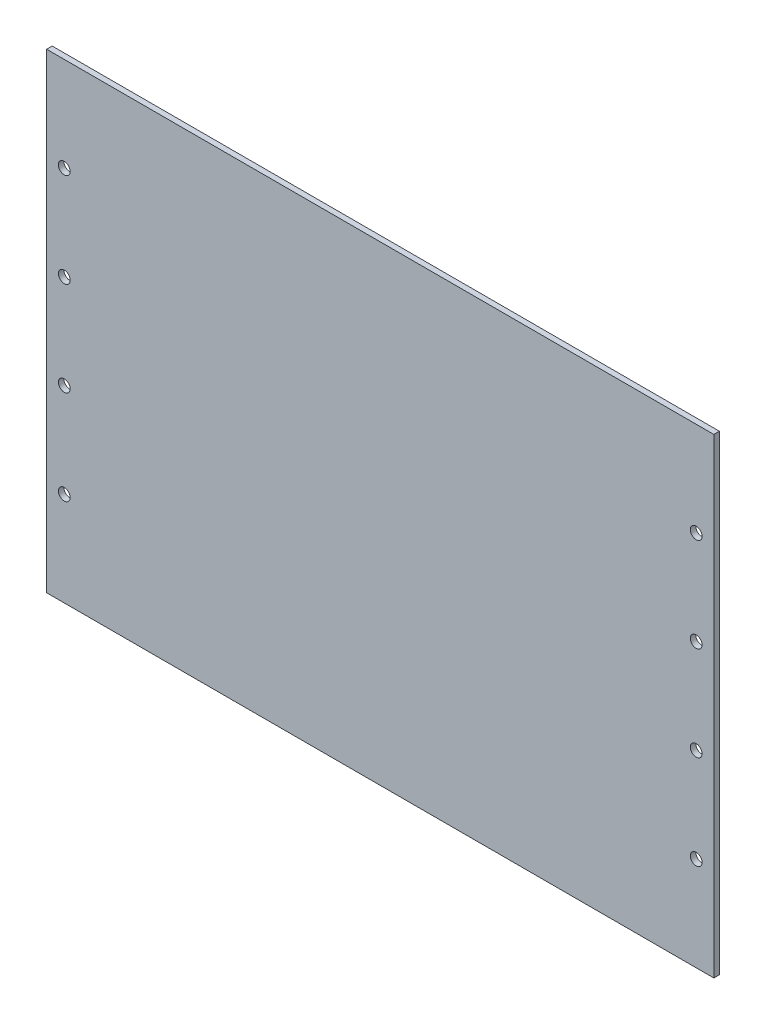
SolidWorks part; units mm, degrees
ref_plane "Front Plane" through (0, 0, 0) normal (0, 0, 1) x (1, 0, 0)
ref_plane "Top Plane" through (0, 0, 0) normal (0, 1, 0) x (1, 0, 0)
ref_plane "Right Plane" through (0, 0, 0) normal (1, 0, 0) x (0, 0, -1)
sketch "Sketch1" plane through (0, 0, 0) normal (0, 0, 1) x (1, 0, 0)
  line L0 (0, -63.5) -> (0, 63.5) construction
  line L1 (-90, 63.5) -> (90, 63.5)
  line L2 (-90, 63.5) -> (-90, -63.5)
  line L3 (-90, -63.5) -> (90, -63.5)
  line L4 (90, 63.5) -> (90, -63.5)
  line L5 (-90, 63.5) -> (90, -63.5) construction
  line L6 (-90, -63.5) -> (90, 63.5) construction
  circle A0 centre (-85.2375, -38.1) radius 1.5875
  circle A1 centre (-85.2375, -12.7) radius 1.5875
  circle A2 centre (-85.2375, 12.7) radius 1.5875
  circle A3 centre (-85.2375, 38.1) radius 1.5875
  circle A4 centre (85.2375, 38.1) radius 1.5875
  circle A5 centre (85.2375, 12.7) radius 1.5875
  circle A6 centre (85.2375, -12.7) radius 1.5875
  circle A7 centre (85.2375, -38.1) radius 1.5875
  point P0 (0, 0)
  point P8 (0, 0)
  dimension "D3" = 3.175
  dimension "D1" = 180
  dimension "D2" = 127
  dimension "D4" = 25.4
  dimension "D5" = 4.7625
  dimension "D7" = 50.8
  dimension "D6" = 4
extrude "Boss-Extrude1" add sketch "Sketch1" along normal blind 1.5
equation "\"Top Plate WIdth\" = 4.5in"
equation "\"Plate Width\" = 5in"
equation "\"Plate Thickness\" = 0.375in"
equation "\"Num holes\" = 4"
equation "\"Plate Height\" = 1.25in"
equation "\"D2@Sketch1\"=\"Plate Width\""
equation "\"Plate Clearance Hole Diameter\" = 0.125in"
equation "\"D3@Sketch1\"=\"Plate Clearance Hole Diameter\""
equation "\"Hole Spacing\"= \"Plate Width\" / ( \"Num holes\" + 1 )"
equation "\"D5@Sketch1\"=\"Plate Thickness\" / 2"
equation "\"D4@Sketch1\"=\"Hole Spacing\""
equation "\"D7@Sketch1\"= 2 * \"Hole Spacing\""
